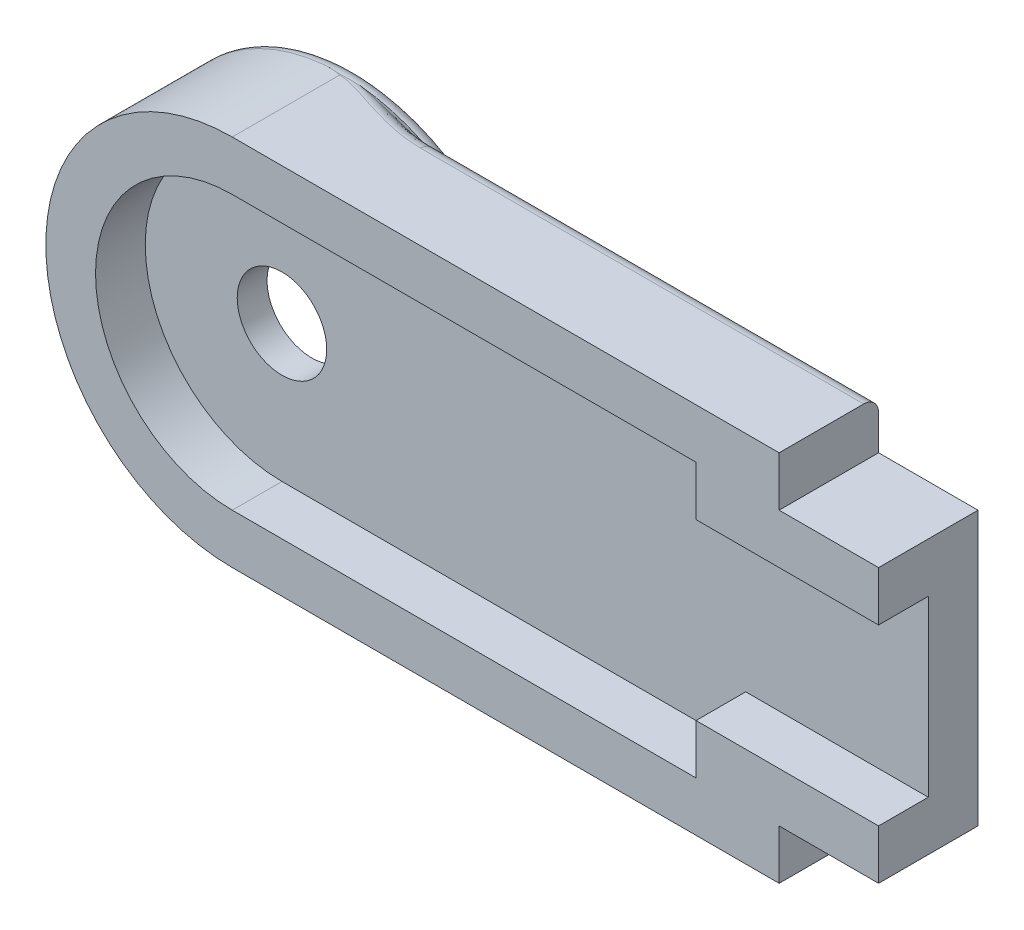
SolidWorks part; units mm, degrees
ref_plane "Спереди" through (0, 0, 0) normal (0, 0, 1) x (1, 0, 0)
ref_plane "Сверху" through (0, 0, 0) normal (0, 1, 0) x (1, 0, 0)
ref_plane "Справа" through (0, 0, 0) normal (1, 0, 0) x (0, 0, -1)
sketch "Эскиз1" plane through (0, 0, 0) normal (0, 0, 1) x (1, 0, 0)
  line L0 (0, 27.5) -> (130, 27.5)
  line L1 (0, -27.5) -> (130, -27.5)
  line L2 (130, -27.5) -> (130, 27.5)
  line L3 (0, 37.5) -> (110, 37.5)
  line L4 (110, 37.5) -> (110, 27.5)
  line L5 (0, -37.5) -> (110, -37.5)
  line L6 (110, -37.5) -> (110, -27.5)
  circle A0 centre (0, 0) radius 27.5
  circle A1 centre (0, 0) radius 37.5
  dimension "D2" = 55
  dimension "D3" = 10
  dimension "D1" = 130
  dimension "D4" = 20
  dimension "D5" = 20
extrude "Бобышка-Вытянуть1" add sketch "Эскиз1" along normal blind 20 contours A1 L1 L2 L0 | A0 | L1 A1 L0 A0 | L0 A1 L1 A0 | A1 L0 L4 L3 | A1 L5 L6 L1
sketch "Эскиз3" plane through (0, 0, 0) normal (0, 0, -1) x (-1, 0, 0)
  line L0 (0, 17.5) -> (-130, 17.5)
  line L1 (-130, -27.5) -> (-130, 27.5) construction
  line L2 (0, -17.5) -> (-130, -17.5)
  line L3 (-130, 17.5) -> (-130, -17.5)
  line L4 (-93.2785, 17.5) -> (-93.2785, 27.5)
  line L5 (-93.2785, 27.5) -> (0, 27.5)
  line L6 (-93.2785, -17.5) -> (-93.2785, -27.5)
  line L7 (-93.2785, -27.5) -> (0, -27.5)
  circle A0 centre (0, 0) radius 17.5
  arc A1 (0, -37.5) -> (0, 37.5) centre (0, 0) ccw construction
  circle A2 centre (0, 0) radius 27.5
  point P19 (0, 27.5)
  point P20 (0, -27.5)
  line M4 (-130, 27.5) -> (-130, -27.5)
  dimension "D1" = 20
  dimension "D2" = 10
extrude "Вырез-Вытянуть2" cut sketch "Эскиз3" against normal blind 10 contours A0 | A0 L0 L2 M4 | A2 L0 A0 L2 | A2 L5 L4 L0 | L0 A2 L2 A0 | A2 L2 L6 L7
sketch "Эскиз5" plane through (0, 0, 20) normal (0, 0, 1) x (1, 0, 0)
  circle A0 centre (0, 0) radius 27.5
  circle A1 centre (0, 0) radius 37.5
  dimension "D1" = 55
extrude "Бобышка-Вытянуть2" add sketch "Эскиз5" along normal blind 5
sketch "Эскиз10" plane through (0, 0, 20) normal (0, 0, 1) x (1, 0, 0)
  line L1 (-21.15, -21.15) -> (21.15, -21.15)
  line L2 (-21.15, -21.15) -> (-21.15, 21.15)
  line L3 (-21.15, 21.15) -> (21.15, 21.15)
  line L4 (21.15, -21.15) -> (21.15, 21.15)
  line L5 (-21.15, -21.15) -> (21.15, 21.15) construction
  line L6 (-21.15, 21.15) -> (21.15, -21.15) construction
  point P0 (0, 0)
  dimension "D1" = 42.3
  dimension "D2" = 42.3
extrude "Вырез-Вытянуть3" cut sketch "Эскиз10" against normal blind 2 and the other way blind 5
sketch "Эскиз11" plane through (0, 0, 18) normal (0, 0, 1) x (1, 0, 0)
  circle A0 centre (0, 0) radius 12
  dimension "D1" = 24
extrude "Вырез-Вытянуть4" cut sketch "Эскиз11" against normal blind 2
sketch "Эскиз12" plane through (0, 0, 16) normal (0, 0, 1) x (1, 0, 0)
  circle A0 centre (0, 0) radius 9
  dimension "D1" = 18
extrude "Вырез-Вытянуть5" cut sketch "Эскиз12" against normal through all
fillet "Скругление1" radius 3 1 edges at (37.5, 0, 25)
fillet "Скругление2" radius 3 1 edges at (37.5, 0, 20)
fillet "Скругление3" radius 3 4 edges at (62.4184, -37.5, 20) (8.8368, -37.5, 20.601) (6, 37.5, 21.137) (62.4184, 37.5, 20)
ref_plane "Плоскость3" through (0, 0, 0) normal (0, 0, -1) x (-1, 0, 0)
mirror "Зеркальное отражение2" about plane through (0, 0, 0) normal (0, 0, -1) of bodies 110
sketch "Эскиз13" plane through (0, 0, 0) normal (0, 0, -1) x (-1, 0, 0)
  line L1 (-443.08, 227.7073) -> (98.009, 227.7073)
  line L2 (-443.08, 227.7073) -> (-443.08, -71.2206)
  line L3 (-443.08, -71.2206) -> (98.009, -71.2206)
  line L4 (98.009, 227.7073) -> (98.009, -71.2206)
  line L5 (-443.08, 227.7073) -> (98.009, -71.2206) construction
  line L6 (-443.08, -71.2206) -> (98.009, 227.7073) construction
  point P0 (-172.5355, 78.2434)
extrude "Вырез-Вытянуть6" cut sketch "Эскиз13" against normal through all
